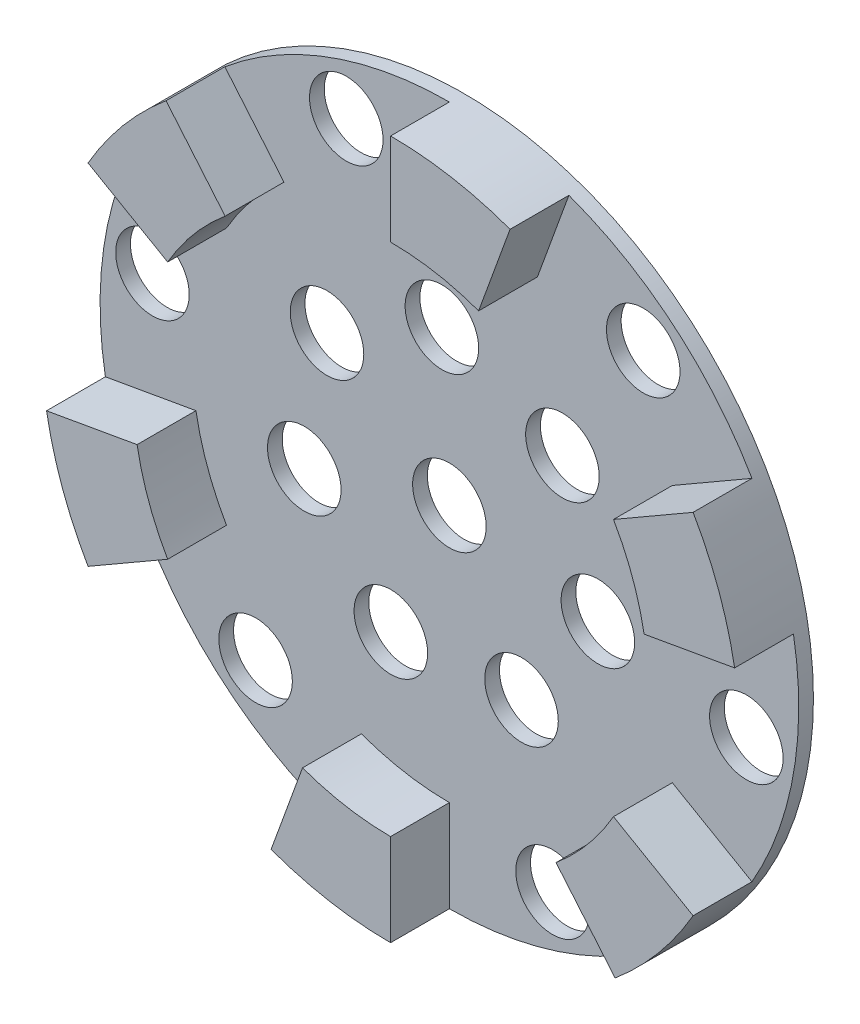
SolidWorks part; units mm, degrees
ref_plane "Ön Düzlem" through (0, 0, 0) normal (0, 0, 1) x (1, 0, 0)
ref_plane "Üst Düzlem" through (0, 0, 0) normal (0, 1, 0) x (1, 0, 0)
ref_plane "Sağ Düzlem" through (0, 0, 0) normal (1, 0, 0) x (0, 0, -1)
sketch "Sketch1" plane through (0, 0, 0) normal (0, 0, 1) x (1, 0, 0)
  line L0 (0, 35) -> (0, 47.5)
  line L1 (11.9707, 32.8892) -> (16.246, 44.6354)
  line L3 (30.3109, 17.5) -> (41.1362, 23.75)
  line L4 (34.4683, 6.0777) -> (46.7784, 8.2483)
  line L6 (30.3109, -17.5) -> (41.1362, -23.75)
  line L7 (22.4976, -26.8116) -> (30.5324, -36.3871)
  line L9 (0, -35) -> (0, -47.5)
  line L10 (-11.9707, -32.8892) -> (-16.246, -44.6354)
  line L12 (-30.3109, -17.5) -> (-41.1362, -23.75)
  line L13 (-34.4683, -6.0777) -> (-46.7784, -8.2483)
  line L15 (-30.3109, 17.5) -> (-41.1362, 23.75)
  line L16 (-22.4976, 26.8116) -> (-30.5324, 36.3871)
  line L18 (22.4976, 26.8116) -> (30.5324, 36.3871) [skipped]
  line L19 (34.4683, -6.0777) -> (46.7784, -8.2483) [skipped]
  line L20 (11.9707, -32.8892) -> (16.246, -44.6354) [skipped]
  line L21 (-22.4976, -26.8116) -> (-30.5324, -36.3871) [skipped]
  line L22 (-34.4683, 6.0777) -> (-46.7784, 8.2483) [skipped]
  line L23 (-11.9707, 32.8892) -> (-16.246, 44.6354) [skipped]
  circle A0 centre (0, 0) radius 47.5
  circle A1 centre (0, 0) radius 35
  circle A2 centre (0, 0) radius 5
  circle A3 centre (20.1886, -3.5598) radius 5
  circle A4 centre (40.3771, -7.1196) radius 5
  circle A5 centre (9.8042, -18.0035) radius 5
  circle A6 centre (-7.9629, -18.8903) radius 5
  circle A7 centre (-19.7338, -5.5522) radius 5
  circle A8 centre (-16.6447, 11.9667) radius 5
  circle A9 centre (-1.0218, 20.4745) radius 5
  circle A10 centre (15.3705, 13.5646) radius 5
  circle A11 centre (31.4078, -26.3543) radius 5
  circle A12 centre (14.0228, -38.5274) radius 5
  circle A13 centre (-7.1196, -40.3771) radius 5
  circle A14 centre (-26.3543, -31.4078) radius 5
  circle A15 centre (-38.5274, -14.0228) radius 5
  circle A16 centre (-40.3771, 7.1196) radius 5
  circle A17 centre (-31.4078, 26.3543) radius 5
  circle A18 centre (-14.0228, 38.5274) radius 5
  circle A19 centre (7.1196, 40.3771) radius 5
  circle A20 centre (26.3543, 31.4078) radius 5
  circle A21 centre (38.5274, 14.0228) radius 5
  dimension "D1" = 18
  dimension "D2" = 3
  dimension "D3" = 7
  dimension "D4" = 12
extrude "Boss-Extrude1" add sketch "Sketch1" along normal blind 2 contours A1 L0 A0 L16 A18 | A1 L3 A0 L1 A20 | A1 L6 A0 L4 A4 | A1 A10 A9 A8 A7 A6 A5 A3 A2 | A1 L9 A0 L7 A12 | A1 L12 A0 L10 A14 | A1 L15 A0 L13 A16 region at (-5.8284, 41.1379, 0) region at (5.9058, 33.4934, 0) region at (19.5469, 36.6635, 0) region at (-21.9781, 35.2599, 0) region at (32.7122, 25.6165, 0) region at (-38.5407, 15.5214, 0) region at (41.525, 1.4037, 0) region at (-41.525, -1.4037, 0) region at (38.5407, -15.5214, 0) region at (-32.7122, -25.6165, 0) region at (-19.5469, -36.6635, 0) region at (21.9781, -35.2599, 0) region at (5.8284, -41.1379, 0)
extrude "Boss-Extrude2" add sketch "Sketch1<3>" along normal blind 10 contours A1 L16 A0 L15 A17 | A1 L13 A0 L12 A15 | A1 L10 A0 L9 A13 | A1 L7 A0 L6 A11 | A1 L4 A0 L3 A21 | A1 L1 A0 L0 A19 | A19 | A17 | A15 | A13 | A11 | A21 region at (0.2185, 41.25, 0) region at (-27.0148, 22.6681, 0) region at (35.8443, 20.4158, 0) region at (-33.1162, -12.0533, 0) region at (35.5909, -20.8548, 0) region at (-6.1156, -34.6834, 0) region at (31.4078, -26.3543, 0) region at (-7.1196, -40.3771, 0) region at (-38.5274, -14.0228, 0) region at (-31.4078, 26.3543, 0) region at (7.1196, 40.3771, 0) region at (38.5274, 14.0228, 0)
sketch "Sketch1<3>" plane through (0, 0, 0) normal (0, 0, 1) x (1, 0, 0) same geometry as "Sketch1"
